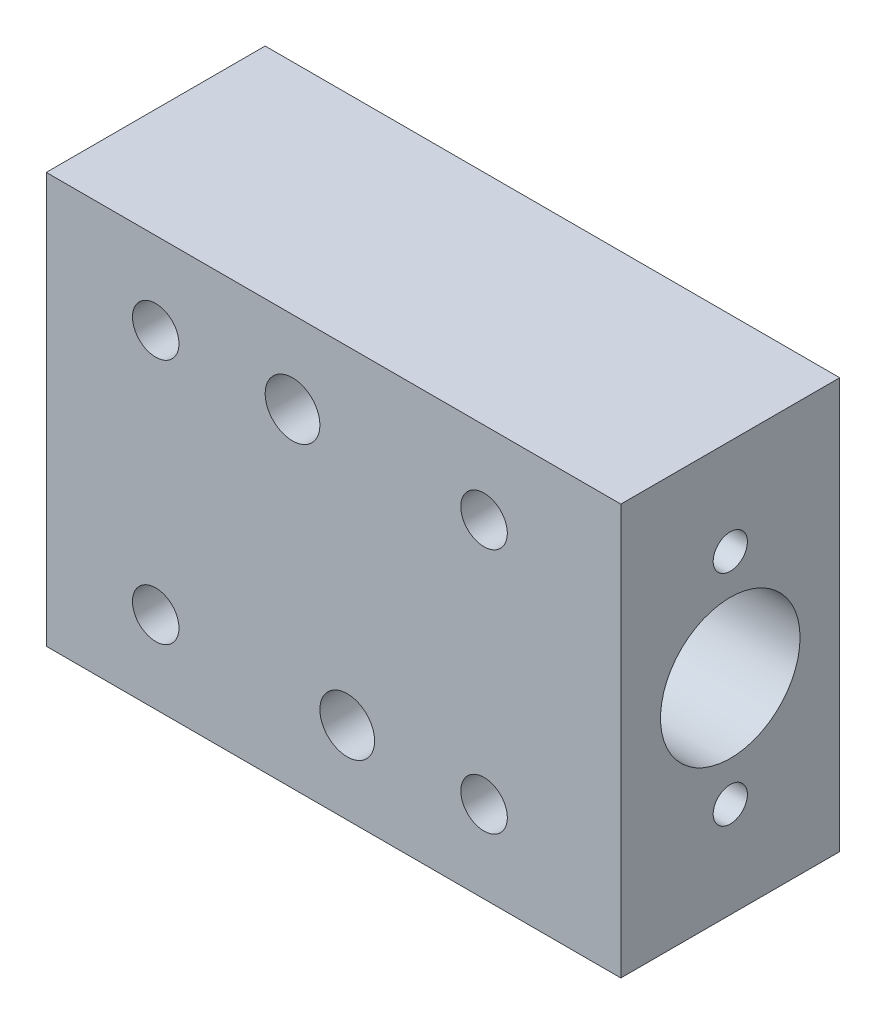
SolidWorks part; units mm, degrees
ref_plane "Alzado" through (0, 0, 0) normal (0, 0, 1) x (1, 0, 0)
ref_plane "Planta" through (0, 0, 0) normal (0, 1, 0) x (1, 0, 0)
ref_plane "Vista lateral" through (0, 0, 0) normal (1, 0, 0) x (0, 0, -1)
sketch "Croquis1" plane through (0, 0, 0) normal (0, 0, 1) x (1, 0, 0)
  line L1 (0, 0) -> (42, 0)
  line L2 (0, 0) -> (0, 30)
  line L3 (0, 30) -> (42, 30)
  line L4 (42, 0) -> (42, 30)
  dimension "D1" = 30
  dimension "D2" = 42
extrude "Saliente-Extruir1" add sketch "Croquis1" along normal blind 16
sketch "Croquis2" plane through (42, 0, 0) normal (1, 0, 0) x (0, 0, -1)
  line L0 (0, 0) -> (0, 30) construction
  line L1 (-16, 0) -> (0, 0) construction
  circle A0 centre (-8, 15) radius 5.1
  dimension "D1" = 10.2
  dimension "D2" = 8
  dimension "D3" = 15
extrude "Cortar-Extruir1" cut sketch "Croquis2" against normal through all
hole_wizard "Refrentado para tornillo con cabeza hueca de M31" positions "Croquis3" profile "Croquis4" counterbore size "M3" standard "DIN" end condition through all
sketch "Croquis3" plane through (0, 0, 0) normal (0, 0, -1) x (-1, 0, 0)
  line L0 (0, 0) -> (-42, 0) construction
  line L1 (-42, 0) -> (-42, 30) construction
  line L2 (0, 30) -> (0, 0) construction
  line L3 (-42, 30) -> (0, 30) construction
  point P0 (-8, 6)
  point P2 (-32, 6)
  point P4 (-32, 24)
  point P6 (-8, 24)
  dimension "D1" = 6
  dimension "D2" = 10
  dimension "D3" = 8
  dimension "D4" = 6
  dimension "D5" = 6
  dimension "D6" = 10
  dimension "D7" = 8
  dimension "D8" = 6
sketch "Croquis4" plane through (8, 6, 0) normal (1, 0, 0) x (0, 1, 0)
  line L0 (0, 0) -> (0, 16)
  line L1 (0, 16) -> (1.7, 16)
  line L3 (1.7, 16) -> (1.7, 3.4)
  line L4 (1.7, 3.4) -> (3.25, 3.4)
  line L5 (3.25, 3.4) -> (3.25, 0)
  line L7 (3.25, 0) -> (0, 0)
  line L11 (0, -6.35) -> (0, 107.95) construction
  dimension "Diámetro de taladro hasta el siguiente" = 3.4
  dimension "Profundidad de taladro hasta el siguiente" = 16
  dimension "Diámetro de refrentado" = 6.5
  dimension "Profundidad de refrentado" = 3.4
hole_wizard "Diámetro de taladro Ø4.0 (4)1" positions "Croquis5" profile "Croquis6" hole size "Ø4.0" standard "DIN" end condition through all
sketch "Croquis5" plane through (0, 0, 0) normal (0, 0, -1) x (-1, 0, 0)
  line L0 (0, 0) -> (-42, 0) construction
  line L1 (-42, 0) -> (-42, 30) construction
  line L2 (-42, 30) -> (0, 30) construction
  point P0 (-22, 6)
  point P2 (-18, 24)
  dimension "D1" = 6
  dimension "D2" = 20
  dimension "D3" = 6
  dimension "D4" = 24
sketch "Croquis6" plane through (22, 6, 0) normal (1, 0, 0) x (0, 1, 0)
  line L0 (0, 0) -> (0, 16)
  line L1 (0, 16) -> (2, 16)
  line L2 (2, 16) -> (2, 0)
  line L5 (2, 0) -> (0, 0)
  line L11 (0, -6.35) -> (0, 107.95) construction
  dimension "Diámetro de taladro hasta el siguiente" = 4
  dimension "Profundidad de taladro hasta el siguiente" = 16
sketch "Croquis7" plane through (42, 0, 0) normal (1, 0, 0) x (0, 0, -1)
  line L0 (-8, 30) -> (-8, 0) construction
  line L1 (-16, 30) -> (0, 30) construction
  line L2 (-16, 0) -> (0, 0) construction
  circle A0 centre (-8, 23) radius 1.25
  circle A1 centre (-8, 7) radius 1.25
  circle A2 centre (-8, 15) radius 8 construction
  point P10 (-8, 25)
  point P11 (-8, 4.3907)
  point P14 (-8, 5)
  dimension "D1" = 16
  dimension "D2" = 2.5
  dimension "D3" = 2.5
extrude "Cortar-Extruir2" cut sketch "Croquis7" against normal blind 7
